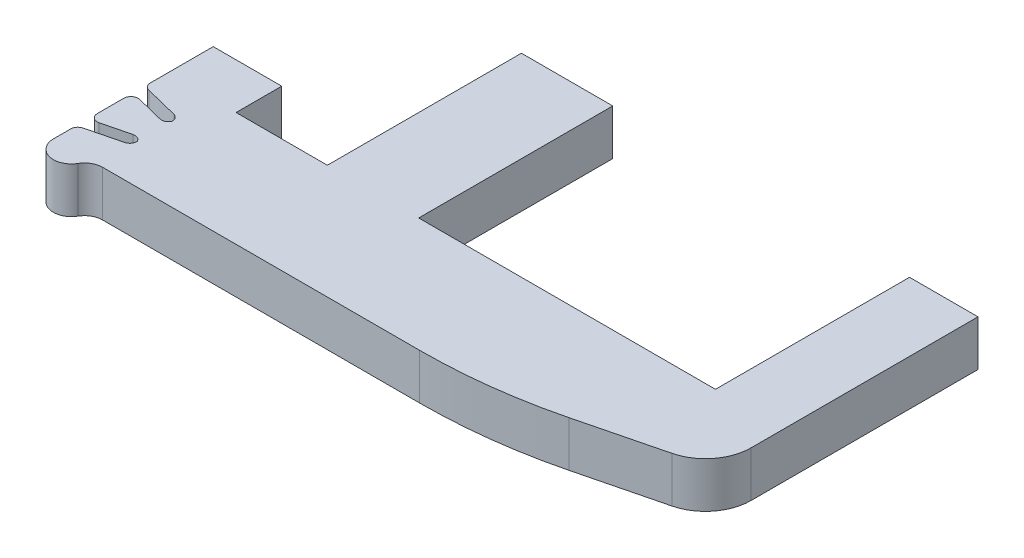
SolidWorks part; units mm, degrees
ref_plane "Front Plane" through (0, 0, 0) normal (0, 0, 1) x (1, 0, 0)
ref_plane "Top Plane" through (0, 0, 0) normal (0, 1, 0) x (1, 0, 0)
ref_plane "Right Plane" through (0, 0, 0) normal (1, 0, 0) x (0, 0, -1)
sketch "Sketch2" plane through (0, 0, 0) normal (0, 0, 1) x (1, 0, 0)
  line L0 (-33.925, 56.4924) -> (-33.925, -23.0187) construction
  line L1 (48.625, -23.0187) -> (-33.925, -23.0187)
  line L3 (48.625, -29.3687) -> (-33.925, -29.3687)
  line L4 (-33.925, -23.0187) -> (-33.925, -29.3687)
  line L6 (48.625, -29.3687) -> (51.8, -29.3687)
  line L8 (48.625, -23.0187) -> (51.8, -23.0187)
  line L9 (51.8, -29.3687) -> (51.8, -23.0187)
  dimension "D1" = 3.175
extrude "Boss-Extrude1" add sketch "Sketch2" along normal blind 15.875
sketch "Sketch3" plane through (0, 0, 0) normal (0, 0, -1) x (-1, 0, 0)
  line L0 (-51.8, -23.0187) -> (33.925, -23.0187) construction
  line L1 (11.7, -23.0187) -> (-1, -23.0187)
  line L2 (11.7, -23.0187) -> (11.7, -29.3687)
  line L3 (11.7, -29.3687) -> (-1, -29.3687)
  line L4 (-1, -23.0187) -> (-1, -29.3687)
  line L5 (11.7, -23.0187) -> (11.7, -29.3687) construction
  line L6 (33.925, -29.3687) -> (-51.8, -29.3687) construction
  line L7 (-1, -1.3969) -> (-1, -29.3687) construction
  line L9 (33.925, -29.3687) -> (-51.8, -29.3687) construction
  line L10 (-42.275, -29.3687) -> (-51.8, -29.3687)
  line L11 (-42.275, -29.3687) -> (-42.275, -23.0187)
  line L12 (-42.275, -23.0187) -> (-51.8, -23.0187)
  line L14 (-51.8, -29.3687) -> (-51.8, -23.0187)
  line L15 (-42.275, -1.3969) -> (-42.275, -29.3687) construction
  dimension "D1" = 6.35
  dimension "D2" = 9.525
extrude "Boss-Extrude2" add sketch "Sketch3" along normal up to surface (26.9875 mm away)
sketch "Sketch5" plane through (0, -23.0187, 0) normal (0, 1, 0) x (1, 0, 0)
  line L0 (51.8, -15.875) -> (-33.925, -15.875) construction
  line L1 (-33.925, -15.875) -> (-33.925, 0) construction
  circle A0 centre (-31.425, -15.875) radius 2.5
  dimension "D1" = 5
extrude "Boss-Extrude4" add sketch "Sketch5" against normal blind 6.35
fillet "Fillet1" radius 2.54 1 edges at (-28.925, -26.1937, 15.875)
sketch "Sketch6" plane through (0, -23.0187, 0) normal (0, 1, 0) x (1, 0, 0)
  line L0 (-33.925, -7.9375) -> (48.625, -7.9375) construction
  line L1 (-33.925, -15.875) -> (-33.925, 0) construction
  line L2 (-33.925, -12.7) -> (-33.925, -3.175) construction
  line L3 (-27.575, -11.1125) -> (-27.575, -4.7625) construction
  line L4 (-33.925, -3.175) -> (-27.575, -4.7625)
  line L5 (-34.31, -4.7151) -> (-27.96, -6.3026)
  line L6 (-33.925, -12.7) -> (-27.575, -11.1125)
  line L7 (-34.31, -11.1599) -> (-27.96, -9.5724)
  line L8 (-27.96, -6.3026) -> (-27.575, -4.7625)
  line L9 (-34.31, -4.7151) -> (-33.925, -3.175)
  line L10 (-33.925, -12.7) -> (-34.31, -11.1599)
  line L11 (-27.575, -11.1125) -> (-27.96, -9.5724)
  point P7 (-33.925, -7.9375)
  point P10 (-27.575, -7.9375)
  dimension "D1" = 9.525
  dimension "D2" = 6.35
  dimension "D3" = 6.35
  dimension "D4" = 1.5875
extrude "Cut-Extrude1" cut sketch "Sketch6" against normal through all
fillet "Fillet3" radius 1 8 edges at (-27.575, -26.1938, 11.1125) (-27.96, -26.1938, 9.5724) (-27.96, -26.1938, 6.3026) (-27.575, -26.1938, 4.7625) (-33.925, -26.1938, 3.175) (-33.925, -26.1938, 4.8114) (-33.925, -26.1938, 11.0636) (-33.925, -26.1938, 12.7)
sketch "Sketch7" plane through (0, -29.3688, 0) normal (0, -1, 0) x (-1, 0, 0)
  line L0 (-51.8, -15.875) -> (-51.8, -9.525)
  line L1 (-51.8, -15.875) -> (-51.8, 26.9875) construction
  line L2 (-51.8, -9.525) -> (-26.4, -15.875)
  line L3 (27.0718, -15.875) -> (-51.8, -15.875) construction
  line L4 (-26.4, -15.875) -> (-51.8, -15.875)
  dimension "D1" = 6.35
  dimension "D2" = 25.4
extrude "Cut-Extrude2" cut sketch "Sketch7" against normal blind 6.35
fillet "Fillet4" radius 6.35 1 edges at (51.8, -26.1937, 9.525)
fillet "Fillet5" radius 76.2 1 edges at (26.4, -26.1938, 15.875)
sketch "Sketch8" plane through (0, 0, 0) normal (0, 0, -1) x (-1, 0, 0)
  line L0 (11.7, -23.0187) -> (33.925, -23.0187) construction
  line L1 (33.925, -29.3687) -> (24.4, -29.3687)
  line L2 (33.925, -29.3687) -> (33.925, -23.0187)
  line L3 (33.925, -23.0187) -> (24.4, -23.0187)
  line L4 (24.4, -29.3687) -> (24.4, -23.0187)
  dimension "D1" = 9.525
extrude "Boss-Extrude5" add sketch "Sketch8" along normal blind 6.35
